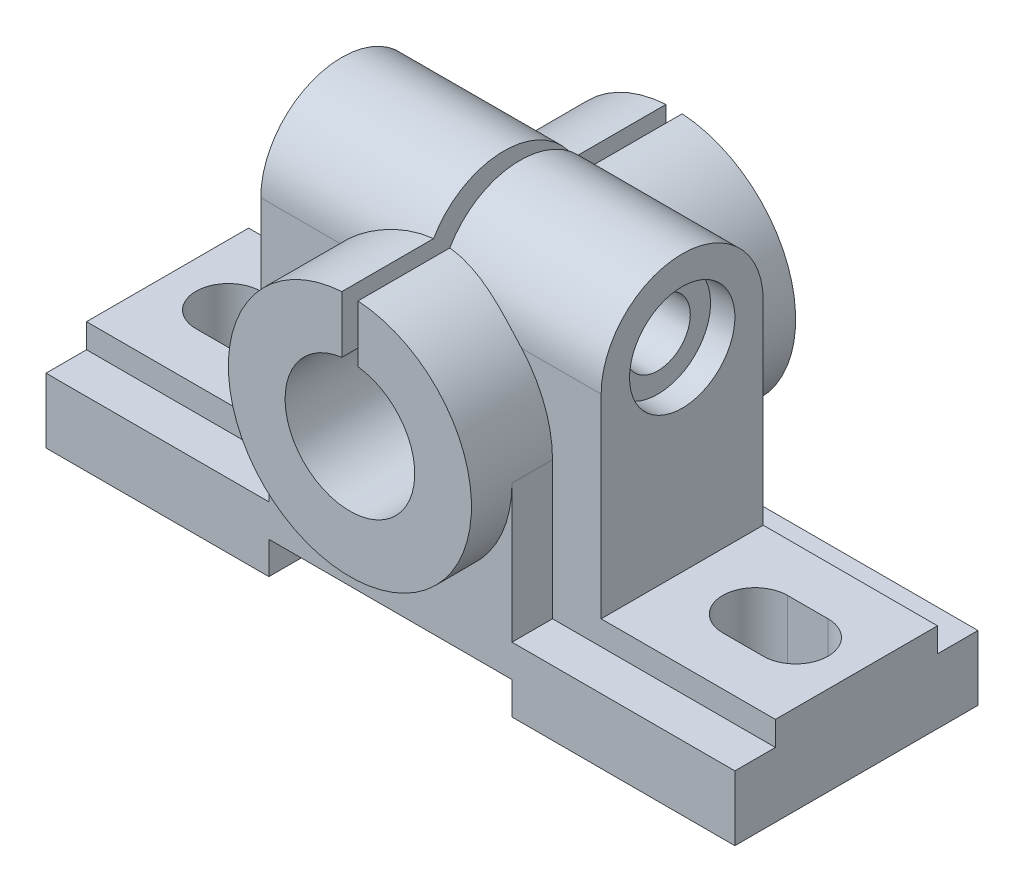
SolidWorks part; units mm, degrees
ref_plane "前视基准面" through (0, 0, 0) normal (0, 0, 1) x (1, 0, 0)
ref_plane "上视基准面" through (0, 0, 0) normal (0, 1, 0) x (1, 0, 0)
ref_plane "右视基准面" through (0, 0, 0) normal (1, 0, 0) x (0, 0, -1)
other "Configuration Table"
sketch "草图1" plane through (0, 0, 0) normal (0, 1, 0) x (1, 0, 0)
  line L1 (-42.5, 15) -> (42.5, 15)
  line L2 (-42.5, 15) -> (-42.5, -15)
  line L3 (-42.5, -15) -> (42.5, -15)
  line L4 (42.5, 15) -> (42.5, -15)
  line L5 (-42.5, 15) -> (42.5, -15) construction
  line L6 (-42.5, -15) -> (42.5, 15) construction
  line L7 (-42.5, 10) -> (42.5, 10)
  line L8 (-42.5, 10) -> (-42.5, -10)
  line L9 (-42.5, -10) -> (42.5, -10)
  line L10 (42.5, 10) -> (42.5, -10)
  line L11 (-42.5, 10) -> (42.5, -10) construction
  line L12 (-42.5, -10) -> (42.5, 10) construction
  point P0 (0, 0)
  point P6 (0, 0)
  dimension "D1" = 30
  dimension "D2" = 85
  dimension "D3" = 20
extrude "凸台-拉伸1" add sketch "草图1" along normal blind 8 contours L2 L7 L4 L1 | L9 L2 L3 L4 region at (0, 0, -12.5) region at (0, 0, 12.5)
extrude "凸台-拉伸2" add sketch "草图1<3>" along normal blind 11 contours L2 L9 L4 L7 region at (0, 0, 0)
sketch "草图1<3>" plane through (0, 0, 0) normal (0, 1, 0) x (1, 0, 0) same geometry as "草图1"
sketch "草图3" plane through (0, 0, 0) normal (1, 0, 0) x (0, 0, -1)
  line L0 (15, 0) -> (-15, 0) construction
  line L1 (-10, 35) -> (-10, 11)
  line L2 (-10, 11) -> (10, 11)
  line L3 (10, 11) -> (10, 35)
  arc A0 (10, 35) -> (-10, 35) centre (0, 35) ccw
  dimension "D1" = 20
  dimension "D2" = 35
extrude "凸台-拉伸3" add sketch "草图3" along normal mid plane 42
sketch "草图6" plane through (-21, 0, 0) normal (-1, 0, 0) x (0, 0, 1)
  circle A0 centre (0, 35) radius 6.5
  circle A1 centre (0, 35) radius 4
  dimension "D1" = 13
  dimension "D2" = 8
extrude "切除-拉伸1" cut sketch "草图6" against normal blind 3
extrude "切除-拉伸2" cut sketch "草图6<2>" against normal blind 21 contours A1
sketch "草图6<2>" plane through (-21, 0, 0) normal (-1, 0, 0) x (0, 0, 1) same geometry as "草图6"
mirror "镜向1" about plane through (0, 0, 0) normal (1, 0, 0) of "切除-拉伸1", "切除-拉伸2"
sketch "草图7" plane through (0, 0, 15) normal (0, 0, 1) x (1, 0, 0)
sketch "草图10" plane through (0, 0, 0) normal (0, 0, 1) x (1, 0, 0)
  line L0 (0, 50.1317) -> (0, -6.1386) construction
  line L1 (0, 0) -> (-15, 0)
  line L2 (-42.5, 0) -> (42.5, 0) construction
  line L3 (-15, 0) -> (-15, 4)
  line L4 (-15, 4) -> (15, 4)
  line L5 (-15, 25) -> (-15, 8)
  line L8 (-15, 8) -> (15, 8)
  line L9 (-42.5, 8) -> (42.5, 8) construction
  line L10 (15, 25) -> (15, 8)
  line L11 (15, 0) -> (15, 4)
  line L12 (0, 0) -> (15, 0)
  circle A0 centre (0, 25) radius 15
  circle A1 centre (0, 25) radius 8
  point P7 (-7.5, 0)
  point P19 (0, 8)
  point P21 (0, 4)
  dimension "D3" = 30
  dimension "D4" = 16
  dimension "D1" = 4
  dimension "D2" = 30
  dimension "D5" = 25
extrude "凸台-拉伸6" add sketch "草图10" along normal mid plane 40 contours L0 A0 A1 | A0 L0 A1 region at (10.3694, 35.3694, 0) region at (-0.3354, 36.5, 0)
extrude "凸台-拉伸7" add sketch "草图10<3>" along normal mid plane 30 contours A0 L0 L8 L10 | L0 A0 L5 L8 region at (10.0593, 11.6833, 0) region at (-10.0593, 11.6833, 0)
sketch "草图10<3>" plane through (0, 0, 0) normal (0, 0, 1) x (1, 0, 0) same geometry as "草图10"
extrude "切除-拉伸4" cut sketch "草图10<4>" against normal mid plane 30 contours L0 A1 | A1 L0 | L0 L4 L3 L1 | L4 L0 L12 L11 region at (7.5, 2, 0) region at (-7.5, 2, 0) region at (3.3953, 25, 0) region at (-3.3953, 25, 0)
sketch "草图10<4>" plane through (0, 0, 0) normal (0, 0, 1) x (1, 0, 0) same geometry as "草图10"
sketch "草图12" plane through (0, 0, 0) normal (0, 1, 0) x (1, 0, 0)
  line L0 (0, 20) -> (0, -20)
  line L1 (15, 20) -> (-15, 20) construction
  line L2 (-15, -20) -> (15, -20) construction
extrude "切除-拉伸-薄壁2" cut sketch "草图12" against normal blind 1 and the other way through all from offset 25 thin thin type mid plane wall 2
sketch "草图14" plane through (0, 11, 0) normal (0, 1, 0) x (1, 0, 0)
  line L0 (0, 25.9139) -> (0, -30.0009) construction
  line L1 (-35, 0) -> (-30, 0) construction
  line L2 (-35, 4) -> (-30, 4)
  line L3 (-35, -4) -> (-30, -4)
  line L6 (-49.9325, 0) -> (48.6886, 0) construction
  line L7 (35, 0) -> (30, 0) construction
  line L8 (35, 4) -> (30, 4)
  line L9 (35, -4) -> (30, -4)
  arc A0 (-35, 4) -> (-35, -4) centre (-35, 0) ccw
  arc A1 (-30, -4) -> (-30, 4) centre (-30, 0) ccw
  arc A2 (35, 4) -> (35, -4) centre (35, 0) cw
  arc A3 (30, -4) -> (30, 4) centre (30, 0) cw
  point P5 (-32.5, 0)
  point P12 (0, 0)
  point P15 (32.5, 0)
  dimension "D1" = 5
  dimension "D2" = 70
  dimension "D3" = 8
extrude "切除-拉伸5" cut sketch "草图14" against normal up to next
extrude "切除-拉伸6" cut sketch "草图6<4>" against normal through all contours A1 region at (-21, 35, 0)
sketch "草图6<4>" plane through (-21, 0, 0) normal (-1, 0, 0) x (0, 0, 1) same geometry as "草图6"
